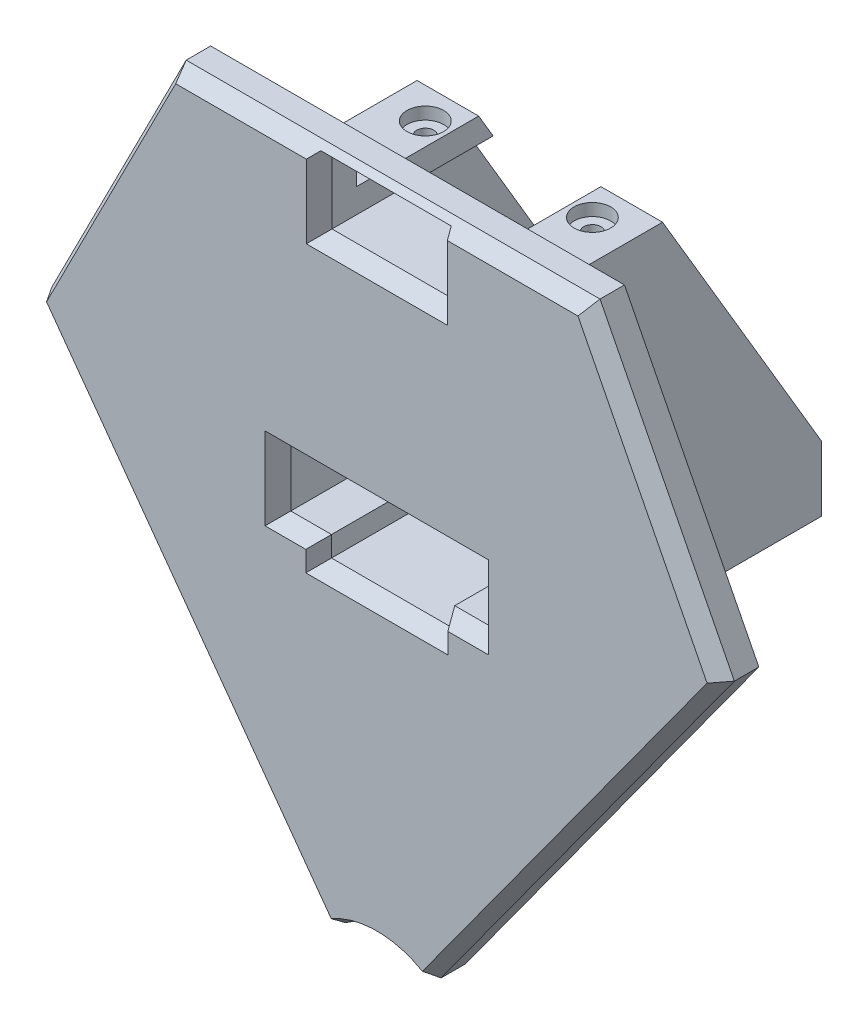
SolidWorks part; units mm, degrees
ref_plane "Front Plane" through (0, 0, 0) normal (0, 0, 1) x (1, 0, 0)
ref_plane "Top Plane" through (0, 0, 0) normal (0, 1, 0) x (1, 0, 0)
ref_plane "Right Plane" through (0, 0, 0) normal (1, 0, 0) x (0, 0, -1)
sketch "Sketch2" plane through (0, 0, 0) normal (0, 1, 0) x (1, 0, 0)
  line L0 (15.061, 0) -> (15.061, 32)
  line L1 (-12.561, 2.5) -> (12.561, 2.5)
  line L2 (-12.561, 2.5) -> (-12.561, 32)
  line L4 (12.561, 2.5) -> (12.561, 32)
  line L5 (15.061, 32) -> (12.561, 32)
  line L7 (-15.061, 32) -> (-15.061, 0)
  line L8 (-15.061, 0) -> (15.061, 0)
  line L10 (-15.061, 32) -> (-12.561, 32)
  point P4 (0, 2.5)
  point P12 (0, 0)
  dimension "D1" = 2.5
  dimension "D2" = 2.5
  dimension "D3" = 29.5
  dimension "D4" = 25.122
extrude "Boss-Extrude1" add sketch "Sketch2" along normal blind 32.5
sketch "Sketch4" plane through (0, 0, 0) normal (0, -1, 0) x (1, 0, 0)
  line L10 (-7.561, -6) -> (-7.561, 0)
  line L13 (-12.561, -2.5) -> (-12.561, -32) construction
  line L18 (-12.561, -10) -> (-7.561, -6)
  line L23 (12.561, -32) -> (12.561, -2.5) construction
  line L26 (12.561, -10) -> (7.561, -6)
  line L33 (-15.061, -32) -> (-15.061, 0) construction
  line L36 (15.061, 0) -> (15.061, -32) construction
  line L38 (-7.561, 0) -> (-15.061, 0)
  line L39 (7.561, -6) -> (7.561, 0)
  line L40 (7.561, 0) -> (15.061, 0)
  line L41 (-15.061, 0) -> (-15.061, -32)
  line L42 (-15.061, -32) -> (-12.561, -32)
  line L43 (-12.561, -32) -> (-15.061, -32) construction
  line L44 (-12.561, -32) -> (-12.561, -10)
  line L45 (12.561, -10) -> (12.561, -32)
  line L46 (12.561, -32) -> (15.061, -32)
  line L47 (15.061, -32) -> (15.061, 0)
  circle A2 centre (-10.2499, -4.95) radius 1.05
  circle A5 centre (10.2499, -4.95) radius 1.05
  dimension "D4" = 6
  dimension "D5" = 2.1
  dimension "D1" = 7.5
  dimension "D2" = 7.5
  dimension "D3" = 10
extrude "Boss-Extrude2" add sketch "Sketch4" along normal blind 2.5
sketch "Sketch5" plane through (0, 32.5, 0) normal (0, 1, 0) x (1, 0, 0)
  line L0 (-15.061, 32) -> (-10.2499, 32)
  line L9 (-10.2499, 32) -> (-6.25, 26)
  line L13 (-15.061, 0) -> (15.061, 0) construction
  line L14 (15.061, 0) -> (-15.061, 0)
  line L15 (-15.061, 0) -> (-15.061, 32)
  line L20 (15.061, 0) -> (15.061, 32)
  line L21 (-6.25, 26) -> (6.25, 26)
  line L22 (6.25, 26) -> (10.2499, 32)
  line L23 (10.2499, 32) -> (15.061, 32)
  circle A0 centre (-10.2499, 4.95) radius 1.05 construction
  circle A1 centre (-10.2499, 8.7) radius 1.05
  circle A2 centre (10.2499, 8.7) radius 1.05
  point P6 (0, 26)
  dimension "D4" = 0
  dimension "D1" = 8.7
  dimension "D2" = 12.5
  dimension "D3" = 20.4998
  dimension "D5" = 6
extrude "Boss-Extrude3" add sketch "Sketch5" along normal blind 3
sketch "Sketch6" plane through (-15.061, 0, 0) normal (-1, 0, 0) x (0, 0, 1)
  line L0 (-12.5, 35.5) -> (-32, 2.5)
  line L1 (-32, 2.5) -> (-32, 35.5)
  line L2 (-32, 35.5) -> (-12.5, 35.5)
  line L3 (-32, 35.5) -> (-32, -2.5) construction
  line L4 (-32, 35.5) -> (0, 35.5) construction
  line L6 (0, -2.5) -> (-32, -2.5) construction
  line L7 (0, 35.5) -> (0, -2.5) construction
  dimension "D1" = 5
  dimension "D2" = 12.5
extrude "Cut-Extrude1" cut sketch "Sketch6" against normal through all
ref_plane "Plane1" through (0, 16.5, 0) normal (0, -1, 0) x (-1, 0, 0)
sketch "Sketch13" plane through (0, 0, 0) normal (0, 0, 1) x (1, 0, 0)
  line L1 (-15.061, 35.5) -> (15.061, 35.5)
  line L2 (-15.061, 35.5) -> (-15.061, -2.5)
  line L3 (-15.061, -2.5) -> (15.061, -2.5)
  line L4 (15.061, 35.5) -> (15.061, -2.5)
extrude "Boss-Extrude7" add sketch "Sketch13" along normal blind 2.5
sketch "Sketch8" plane through (0, 0, 2.5) normal (0, 0, 1) x (1, 0, 0)
  line L0 (0, -48.5) -> (-47.2253, 16.5)
  line L1 (-16.5671, 16.5) -> (16.5671, 16.5) construction
  line L2 (-47.2253, 16.5) -> (47.2253, 16.5)
  line L3 (47.2253, 16.5) -> (0, -48.5)
  dimension "D1" = 72
  dimension "D2" = 65
extrude "Boss-Extrude4" add sketch "Sketch8" along normal blind 5
sketch "Sketch9" plane through (0, 0, 2.5) normal (0, 0, 1) x (1, 0, 0)
  line L0 (47.2253, 16.5) -> (65.3888, 41.5)
  line L1 (65.3888, 41.5) -> (-65.3888, 41.5)
  line L2 (-65.3888, 41.5) -> (-47.2253, 16.5)
  line L3 (47.2253, 16.5) -> (-47.2253, 16.5)
  line L4 (0, -48.5) -> (47.2253, 16.5) construction
  line L5 (-47.2253, 16.5) -> (0, -48.5) construction
  dimension "D1" = 25
extrude "Boss-Extrude6" add sketch "Sketch9" along normal up to surface (5 mm away) up to face at (0, -5.1667, 7.5)
sketch "Sketch10" plane through (0, 0, 2.5) normal (0, 0, -1) x (-1, 0, 0)
  line L25 (-25.3888, 41.5) -> (-65.3888, 41.5)
  line L26 (-65.3888, 41.5) -> (65.3888, 41.5) construction
  line L27 (-65.3888, 41.5) -> (-41.8774, 9.1393)
  line L28 (0, -48.5) -> (-65.3888, 41.5) construction
  line L29 (-41.8774, 9.1393) -> (-25.3888, 41.5)
  line L30 (65.3888, 41.5) -> (41.8774, 9.1393)
  line L31 (65.3888, 41.5) -> (0, -48.5) construction
  line L32 (41.8774, 9.1393) -> (25.3888, 41.5)
  line L33 (25.3888, 41.5) -> (65.3888, 41.5)
  dimension "D1" = 40
extrude "Cut-Extrude2" cut sketch "Sketch10" against normal through all
sketch "Sketch14" plane through (0, 0, -2.5) normal (0, 0, -1) x (-1, 0, 0)
  line L11 (-7.561, -2.5) -> (7.561, -2.5)
  line L12 (15.061, -2.5) -> (-15.061, -2.5) construction
  line L13 (7.561, -2.5) -> (7.561, 0)
  line L14 (12.561, 0) -> (7.561, 0) construction
  line L15 (7.561, -2.5) -> (7.561, 0) construction
  line L16 (7.561, 0) -> (12.561, 0)
  line L17 (12.561, 0) -> (12.561, 7.7837)
  line L18 (12.561, 2.5) -> (12.561, 32.5) construction
  line L19 (12.561, 7.7837) -> (-12.561, 7.7837)
  line L20 (-12.561, 32.5) -> (-12.561, 2.5) construction
  line L21 (-12.561, 7.7837) -> (-12.561, 0)
  line L22 (-12.561, 2.5) -> (-12.561, -2.5) construction
  line L23 (-7.561, 0) -> (-12.561, 0) construction
  line L24 (-12.561, 0) -> (-7.561, 0)
  line L25 (-7.561, 0) -> (-7.561, -2.5)
  line L26 (-7.561, -2.5) -> (-12.561, -2.5) construction
  line L27 (-15.061, 35.5) -> (15.061, 35.5) construction
  line L28 (-7.5, 35.5) -> (7.5, 35.5)
  line L29 (-7.5, 35.5) -> (-7.5, 40.5)
  line L30 (-7.5, 40.5) -> (7.5, 40.5)
  line L31 (7.5, 35.5) -> (7.5, 40.5)
  point P37 (0, 35.5)
  dimension "D1" = 15
  dimension "D2" = 5
extrude "Cut-Extrude3" cut sketch "Sketch14" against normal through all
sketch "Sketch15" plane through (0, -2.5, 0) normal (0, -1, 0) x (1, 0, 0)
  line L1 (15.061, -32) -> (-15.061, -32)
  line L2 (15.061, -32) -> (15.061, 2.5)
  line L3 (15.061, 2.5) -> (-15.061, 2.5)
  line L4 (-15.061, -32) -> (-15.061, 2.5)
  circle A0 centre (-10.2499, -4.95) radius 2.495
  circle A1 centre (10.341, -4.95) radius 2.495
  dimension "D1" = 4.99
  dimension "D2" = 4.99
extrude "Boss-Extrude8" add sketch "Sketch15" along normal blind 3
sketch "Sketch17" plane through (0, -5.5, 0) normal (0, -1, 0) x (1, 0, 0)
  line L0 (15.061, 2.5) -> (-15.061, 2.5) construction
  circle A0 centre (0, -37.5) radius 13.75
  dimension "D2" = 27.5
  dimension "D1" = 40
extrude "Cut-Extrude4" cut sketch "Sketch17" against normal through all
sketch "Sketch19" plane through (0, 0, -2.5) normal (0, 0, -1) x (-1, 0, 0)
  line L0 (-15.061, 35.5) -> (15.061, 35.5) construction
  line L1 (7.5, 35.5) -> (-7.5, 35.5)
  line L2 (7.5, 35.5) -> (7.5, 32.5)
  line L3 (7.5, 32.5) -> (-7.5, 32.5)
  line L4 (-7.5, 35.5) -> (-7.5, 32.5)
  line L5 (7.5, 35.5) -> (7.5, 40.5) construction
  line L6 (-7.5, 40.5) -> (-7.5, 35.5) construction
  line L7 (-12.561, 32.5) -> (12.561, 32.5) construction
  dimension "D1" = 0
  dimension "D2" = 0
  dimension "D3" = 0
extrude "Cut-Extrude6" cut sketch "Sketch19" along normal through all both and the other way through all
sketch "Sketch21" plane through (0, 35.5, 0) normal (0, 1, 0) x (1, 0, 0)
  circle A0 centre (-10.2499, 8.7) radius 2.25
  circle A1 centre (10.2499, 8.7) radius 2.25
  dimension "D1" = 4.5
  dimension "D2" = 4.5
extrude "Cut-Extrude8" cut sketch "Sketch21" against normal blind 1.5
ref_axis "Axis1" through (0, -48.5, 11.5724) along (0, 0, -1)
sketch "Sketch20" plane through (0, 0, 2.5) normal (0, 0, -1) x (-1, 0, 0)
  circle A0 centre (0, -48.5) radius 10
  dimension "D1" = 20
extrude "Cut-Extrude7" cut sketch "Sketch20" against normal through all
chamfer "Chamfer1" distance 2 angle 30 18 edges at (-23.8776, -15.6353, 7.5) (-33.6331, 25.3197, 7.5) (0, 41.5, 7.5) (33.6331, 25.3197, 7.5) (23.8776, -15.6353, 7.5) (7.5, 36.5, 7.5) (0, 40.5, 7.5) (-7.5, 36.5, 7.5) (0, 32.5, 7.5) (12.561, 3.8918, 7.5) (0, 7.7837, 7.5) (-12.561, 3.8918, 7.5) (-10.061, 0, 7.5) (-7.561, -1.25, 7.5) (0, -2.5, 7.5) (7.561, -1.25, 7.5) (10.061, 0, 7.5) (0, -38.5, 7.5) first distance on face at (-23.8776, -15.6353, 5) first distance on face at (-33.6331, 25.3197, 5) first distance on face at (0, 41.5, 5) first distance on face at (33.6331, 25.3197, 5) first distance on face at (23.8776, -15.6353, 5) first distance on face at (7.5, 35.6429, -1.3247) first distance on face at (0, 40.5, 5) first distance on face at (-7.5, 35.6429, -1.3247) first distance on face at (0, 32.5, 2.5) first distance on face at (12.561, 8.6917, -9.7874) first distance on face at (0, 7.7837, 2.5) first distance on face at (-12.561, 8.6917, -9.7874) first distance on face at (-10.061, 0, -0.25) first distance on face at (-7.561, -1.25, 0.75) first distance on face at (0, -2.5, -9.0821) first distance on face at (7.561, -1.25, 0.75) first distance on face at (10.061, 0, -0.25) first distance on face at (0, -39.4549, 5)
